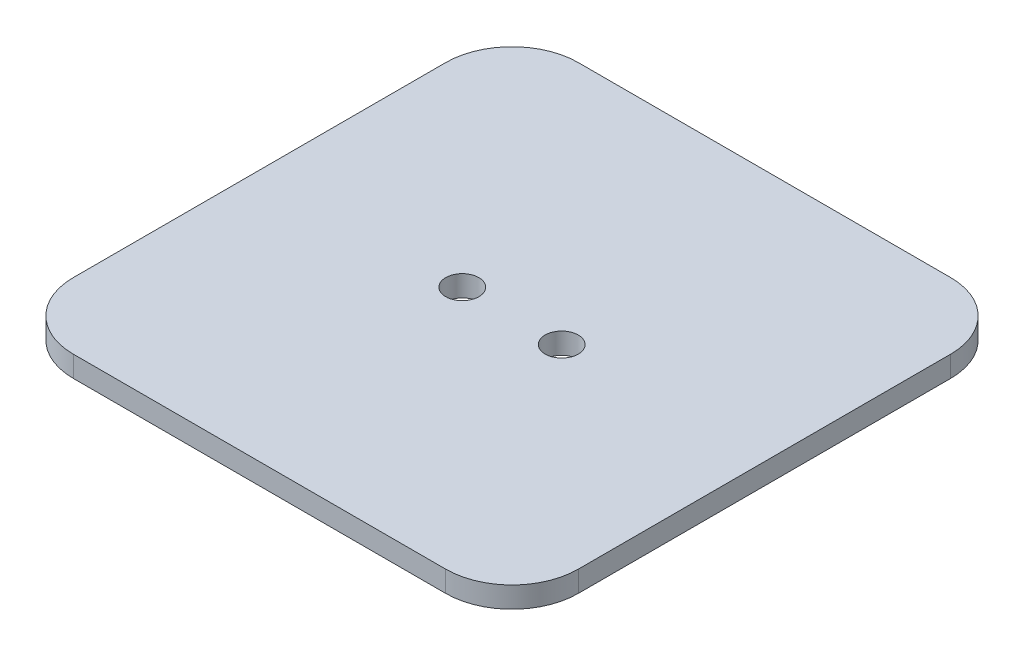
SolidWorks part; units mm, degrees
ref_plane "Front Plane" through (0, 0, 0) normal (0, 0, 1) x (1, 0, 0)
ref_plane "Top Plane" through (0, 0, 0) normal (0, 1, 0) x (1, 0, 0)
ref_plane "Right Plane" through (0, 0, 0) normal (1, 0, 0) x (0, 0, -1)
sketch "Sketch1" plane through (0, 0, 0) normal (0, 1, 0) x (1, 0, 0)
  line L1 (-38.1, -38.1) -> (38.1, -38.1)
  line L2 (-38.1, -38.1) -> (-38.1, 38.1)
  line L3 (-38.1, 38.1) -> (38.1, 38.1)
  line L4 (38.1, -38.1) -> (38.1, 38.1)
  line L5 (-38.1, -38.1) -> (38.1, 38.1) construction
  line L6 (-38.1, 38.1) -> (38.1, -38.1) construction
  point P0 (0, 0)
  dimension "D1" = 76.2
  dimension "D2" = 76.2
extrude "Boss-Extrude1" add sketch "Sketch1" along normal blind 3.175
fillet "Fillet1" radius 10 1 edges at (-38.1, 1.5875, 38.1)
fillet "Fillet2" radius 10 1 edges at (-38.1, 1.5875, -38.1)
fillet "Fillet3" radius 10 1 edges at (38.1, 1.5875, -38.1)
fillet "Fillet4" radius 10 1 edges at (38.1, 1.5875, 38.1)
sketch "Sketch2" plane through (0, 3.175, 0) normal (0, 1, 0) x (1, 0, 0)
  line L0 (-1.7463, 0) -> (1.7463, 0) construction
  line L1 (38.1, -28.1) -> (38.1, 28.1) construction
  circle A0 centre (7.5, 0) radius 2.5
  circle A1 centre (-7.5, 0) radius 2.5
  dimension "D1" = 5
  dimension "D2" = 5
  dimension "D3" = 15
  dimension "D4" = 30.6
extrude "Cut-Extrude1" cut sketch "Sketch2" against normal through all
